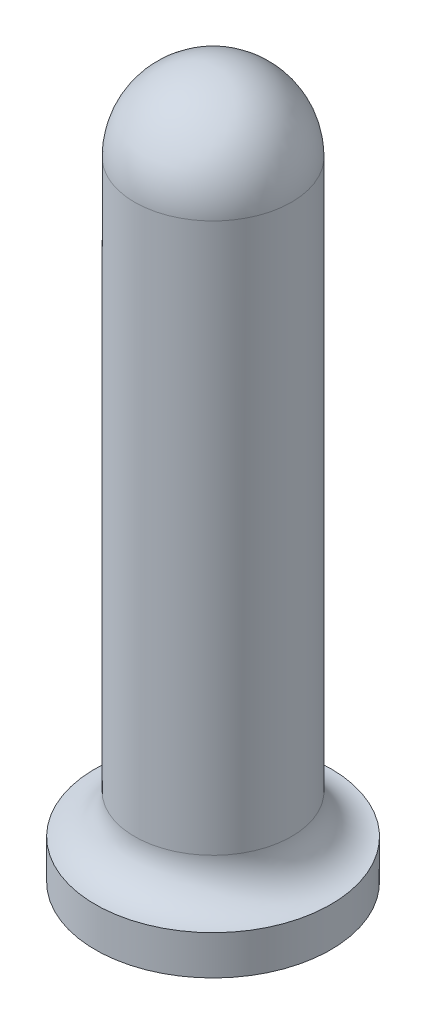
SolidWorks part; units mm, degrees
ref_plane "Front Plane" through (0, 0, 0) normal (0, 0, 1) x (1, 0, 0)
ref_plane "Top Plane" through (0, 0, 0) normal (0, 1, 0) x (1, 0, 0)
ref_plane "Right Plane" through (0, 0, 0) normal (1, 0, 0) x (0, 0, -1)
sketch "Sketch1" plane through (0, 0, 0) normal (0, 1, 0) x (1, 0, 0)
  circle A0 centre (0, 0) radius 2
  dimension "D1" = 4
extrude "Boss-Extrude1" add sketch "Sketch1" along normal blind 15 contours A0
sketch "Sketch2" plane through (0, 0, 0) normal (0, 0, 1) x (1, 0, 0)
  line L0 (2, 15) -> (-2, 15) construction
  line L2 (2, 15) -> (-2, 15)
  arc A2 (2, 15) -> (-2, 15) centre (0, 15) ccw
revolve "Revolve1" add sketch "Sketch2" angle 360 about L2
sketch "Sketch3" plane through (0, 0, 0) normal (0, -1, 0) x (1, 0, 0)
  circle A0 centre (0, 0) radius 3
  point P3 (0, 0)
extrude "Boss-Extrude2" add sketch "Sketch3" along normal blind 1
fillet "Fillet3" radius 1 1 edges at (0, 0, 2)
